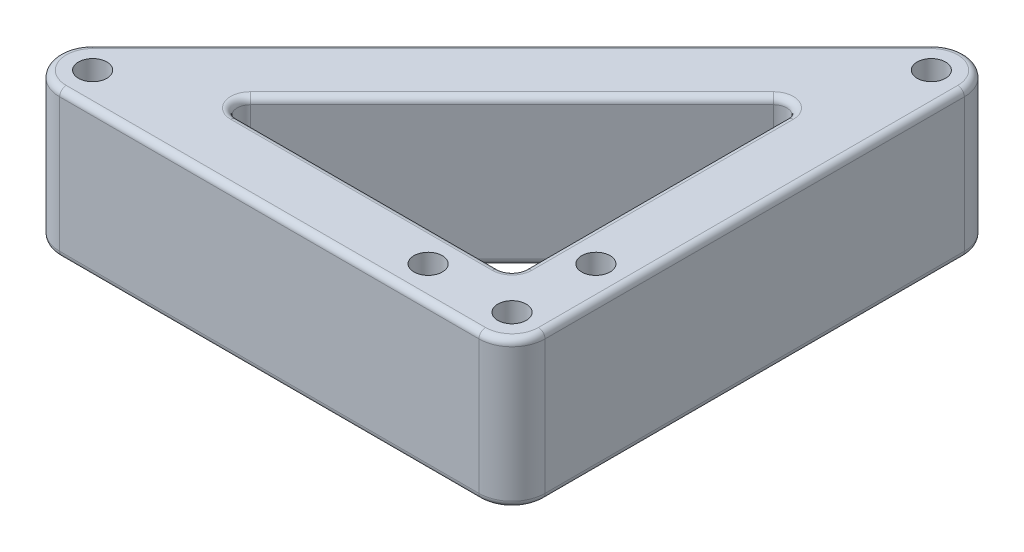
SolidWorks part; units mm, degrees
ref_plane "Front Plane" through (0, 0, 0) normal (0, 0, 1) x (1, 0, 0)
ref_plane "Top Plane" through (0, 0, 0) normal (0, 1, 0) x (1, 0, 0)
ref_plane "Right Plane" through (0, 0, 0) normal (1, 0, 0) x (0, 0, -1)
sketch "Sketch1" plane through (0, 0, 0) normal (0, 1, 0) x (1, 0, 0)
  line L0 (0, 0) -> (63.5, 63.5) construction
  line L1 (0, 0) -> (63.5, 0) construction
  line L2 (0, 0) -> (0, 63.5) construction
  line L3 (0, 63.5) -> (63.5, 63.5) construction
  line L4 (63.5, 0) -> (63.5, 63.5) construction
  line L5 (0, 0) -> (63.5, 63.5) construction
  line L6 (-3.5355, 3.5355) -> (59.9645, 67.0355)
  line L7 (3.5355, -3.5355) -> (67.0355, 59.9645)
  line L8 (0, -5) -> (68.5, -5)
  line L9 (68.5, 63.5) -> (68.5, -5)
  line L10 (0, 5) -> (58.5, 5)
  line L11 (58.5, 63.5) -> (58.5, 5)
  circle A0 centre (0, 0) radius 2.15
  circle A1 centre (63.5, 63.5) radius 2.15
  arc A2 (-3.5355, 3.5355) -> (3.5355, -3.5355) centre (0, 0) ccw
  arc A3 (67.0355, 59.9645) -> (59.9645, 67.0355) centre (63.5, 63.5) ccw
  circle A4 centre (63.5, 0) radius 2.15
  circle A5 centre (63.5, 63.5) radius 5 construction
  circle A6 centre (0, 0) radius 5 construction
  circle A7 centre (50.8, 0) radius 2.15
  circle A8 centre (63.5, 12.7) radius 2.15
  point P7 (31.75, 31.75)
  dimension "D2" = 4.3
  dimension "D3" = 5
  dimension "D1" = 63.5
  dimension "D4" = 12.7
  dimension "D5" = 12.7
extrude "Boss-Extrude1" add sketch "Sketch1" along normal blind 22.2504 contours A3 L7 L11 L10 A2 L8 L9 A4 | L7 A3 L6 A2 A0 A1 region at (31.75, 0, -31.75) region at (1.9505, 0, 4.7089)
fillet "Fillet1" radius 5 1 edges at (68.5, 11.1252, 5)
fillet "Fillet2" radius 2 3 edges at (58.5, 11.1252, -51.4289) (58.5, 11.1252, -5) (12.0711, 11.1252, -5)
fillet "Fillet3" radius 1 24 edges at (15.0517, 0, -6.2346) (36.6997, 0, -5) (57.9142, 0, -5.5858) (58.5, 0, -26.8003) (57.2654, 0, -48.4483) (-4.6194, 0, 1.9134) (28.2145, 0, -35.2855) (65.4134, 0, -68.1194) (68.5, 0, -31.75) (67.0355, 0, 3.5355) (15.0517, 22.2504, -6.2346) (35.2855, 22.2504, -28.2145) (57.2654, 22.2504, -48.4483) (58.5, 22.2504, -26.8003) (57.9142, 22.2504, -5.5858) (-4.6194, 22.2504, 1.9134) (28.2145, 22.2504, -35.2855) (65.4134, 22.2504, -68.1194) (68.5, 22.2504, -31.75) (67.0355, 22.2504, 3.5355) (35.2855, 0, -28.2145) (31.75, 0, 5) (36.6997, 22.2504, -5) (31.75, 22.2504, 5)
